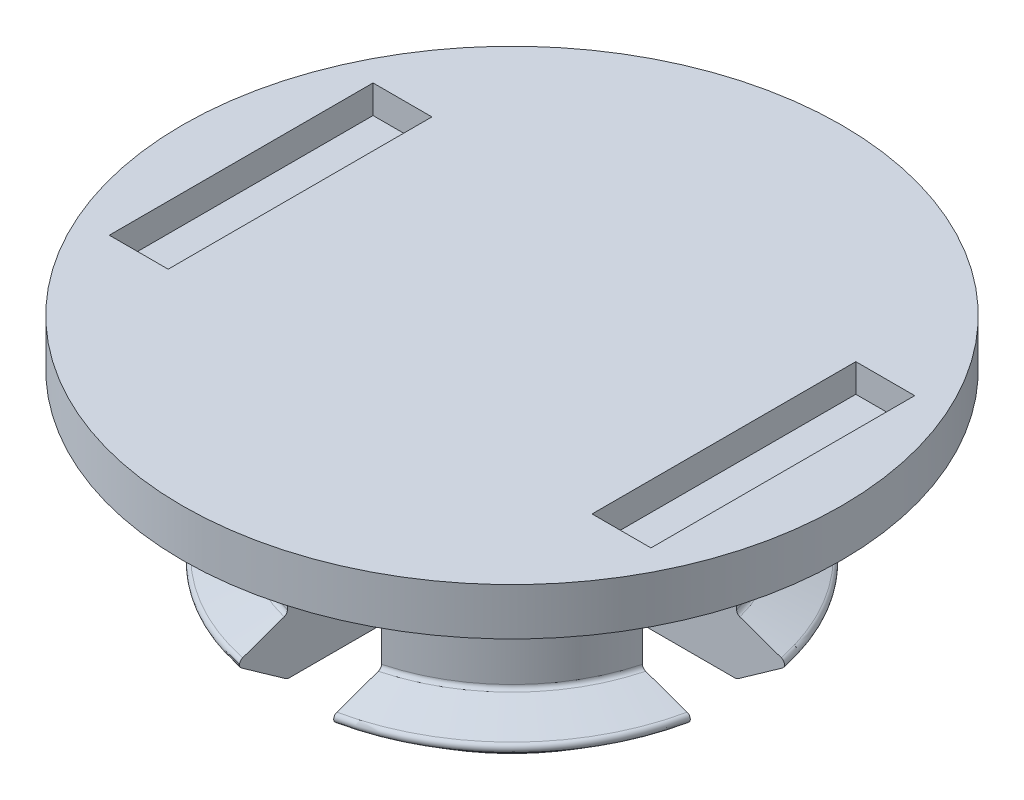
SolidWorks part; units mm, degrees
ref_plane "Front Plane" through (0, 0, 0) normal (0, 0, 1) x (1, 0, 0)
ref_plane "Top Plane" through (0, 0, 0) normal (0, 1, 0) x (1, 0, 0)
ref_plane "Right Plane" through (0, 0, 0) normal (1, 0, 0) x (0, 0, -1)
sketch "Szkic1" plane through (0, 0, 0) normal (0, 1, 0) x (1, 0, 0)
  circle A0 centre (0, 0) radius 7
  dimension "D1" = 14
extrude "Dodanie-wyciągnięcie1" add sketch "Szkic1" along normal blind 1
ref_point "Punkt1"
ref_plane "Płaszczyzna1" through (0, 0, 0) normal (0, -1, 0) x (-1, 0, 0)
sketch "Szkic2" plane through (0, 0, 0) normal (0, -1, 0) x (-1, 0, 0)
  circle A0 centre (0, 0) radius 3.9
  dimension "D1" = 7.8
extrude "Dodanie-wyciągnięcie2" add sketch "Szkic2" along normal blind 4.3
ref_axis "Oś1" through (0, -4.3, 0) along (0, 1, 0)
sketch "Szkic3" plane through (0, 0, 0) normal (1, 0, 0) x (0, 0, -1)
  line L1 (3.9, -4.3) -> (5, -3.5004)
  line L2 (5, -3.5004) -> (3.9, -3.1)
  line L4 (3.9, -3.1) -> (3.9, -4.3)
  line L5 (0, -4.3) -> (0, 0) construction
  line L7 (-7.7, 0) -> (7.7, 0) construction
  dimension "D1" = 3.9
  dimension "D2" = 1.2
  dimension "D3" = 70
  dimension "D4" = 4.3
  dimension "D5" = 5
revolve "Obrót1" add sketch "Szkic3" angle 360 about axis through (0, -4.3, 0) along (0, 1, 0)
fillet "Zaokrąglenie1" radius 0.1 3 edges at (0, -3.5004, -5) (0, -3.1, -3.9) (0, -4.3, -3.9)
ref_plane "Płaszczyzna2" through (0, -4.3, 0) normal (0, -1, 0) x (-1, 0, 0)
sketch "Szkic5" plane through (0, -4.3, 0) normal (0, -1, 0) x (-1, 0, 0)
  line L0 (-7.7941, -1) -> (-1, -1)
  line L1 (7.7941, 1) -> (1, 1)
  line L2 (-1, -7.7941) -> (-1, -1)
  line L3 (1, 7.7941) -> (1, 1)
  line L4 (-1, 1) -> (-1, 7.7941)
  line L5 (1, -1) -> (7.7941, -1)
  line L6 (1, -1) -> (1, -7.7941)
  line L7 (-1, 1) -> (-7.7941, 1)
  line L8 (-1, -1) -> (1, 1) construction
  arc A0 (-7.7941, 1) -> (-7.7941, -1) centre (0, 0) ccw
  arc A1 (-1, -7.7941) -> (1, -7.7941) centre (0, 0) ccw
  arc A2 (7.7941, -1) -> (7.7941, 1) centre (0, 0) ccw
  arc A3 (1, 7.7941) -> (-1, 7.7941) centre (0, 0) ccw
  point P1 (0, 0)
  dimension "D1" = 2
  dimension "D2" = 2
extrude "Wytnij-wyciągnięcie1" cut sketch "Szkic5" against normal blind 4.3
ref_plane "Płaszczyzna3" through (0, 1, 0) normal (0, 1, 0) x (1, 0, 0)
sketch "Szkic8" plane through (0, 1, 0) normal (0, 1, 0) x (1, 0, 0)
  line L0 (4.5, -2.8) -> (-4.5, 2.8) construction
  line L1 (5.75, -2.8) -> (4.5, -2.8)
  line L2 (5.75, -2.8) -> (5.75, 2.8)
  line L3 (5.75, 2.8) -> (4.5, 2.8)
  line L4 (4.5, -2.8) -> (4.5, 2.8)
  line L5 (-4.5, -2.8) -> (-5.75, -2.8)
  line L6 (-4.5, -2.8) -> (-4.5, 2.8)
  line L7 (-4.5, 2.8) -> (-5.75, 2.8)
  line L8 (-5.75, -2.8) -> (-5.75, 2.8)
  point P8 (0, 0)
  dimension "D1" = 5.6
  dimension "D2" = 1.25
  dimension "D3" = 9
extrude "Wytnij-wyciągnięcie2" cut sketch "Szkic8" against normal blind 0.6
